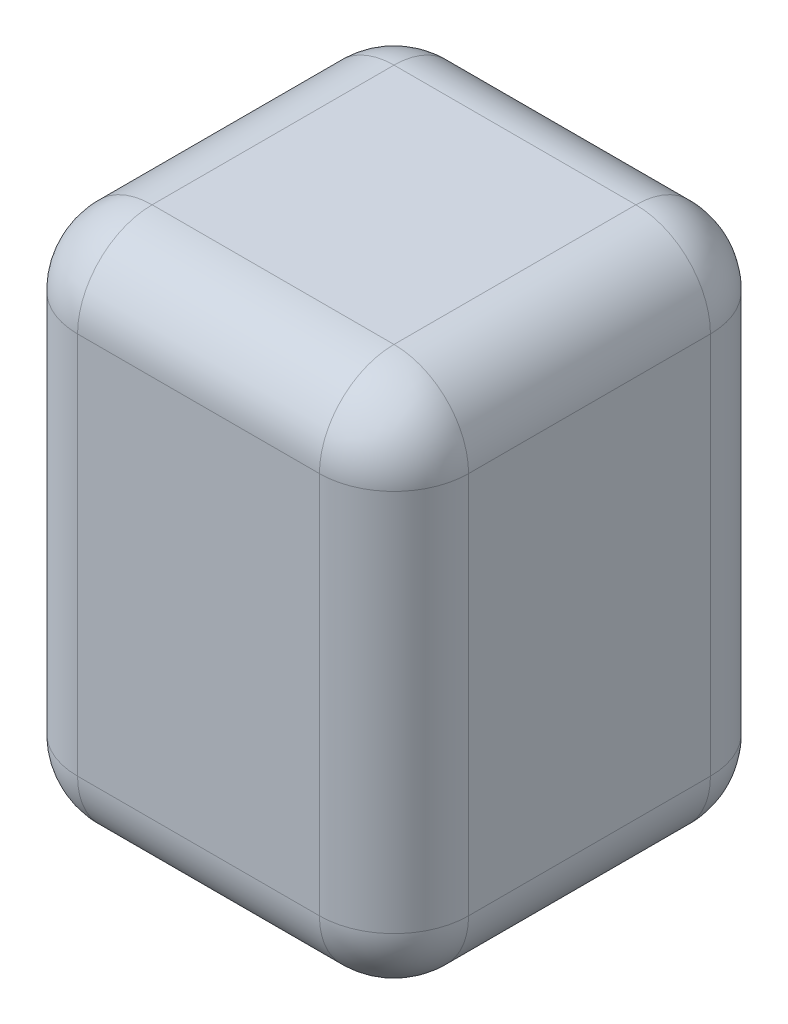
SolidWorks part; units mm, degrees
ref_plane "Front Plane" through (0, 0, 0) normal (0, 0, 1) x (1, 0, 0)
ref_plane "Top Plane" through (0, 0, 0) normal (0, 1, 0) x (1, 0, 0)
ref_plane "Right Plane" through (0, 0, 0) normal (1, 0, 0) x (0, 0, -1)
sketch "Sketch1" plane through (0, 0, 0) normal (0, 1, 0) x (1, 0, 0)
  line L0 (0, 48.5) -> (0, -48.5) construction
  line L1 (-48.5, 48.5) -> (48.5, 48.5)
  line L2 (-48.5, 48.5) -> (-48.5, -48.5)
  line L3 (-48.5, -48.5) -> (48.5, -48.5)
  line L4 (48.5, 48.5) -> (48.5, -48.5)
  line L5 (48.5, 0) -> (-48.5, 0) construction
  dimension "D1" = 97
  dimension "D2" = 97
extrude "Boss-Extrude1" add sketch "Sketch1" along normal blind 132
fillet "Fillet1" radius 18.5 12 edges at (0, 0, -48.5) (48.5, 66, -48.5) (48.5, 0, 0) (-48.5, 66, -48.5) (-48.5, 0, 0) (-48.5, 66, 48.5) (48.5, 66, 48.5) (0, 0, 48.5) (0, 132, -48.5) (48.5, 132, 0) (0, 132, 48.5) (-48.5, 132, 0)
